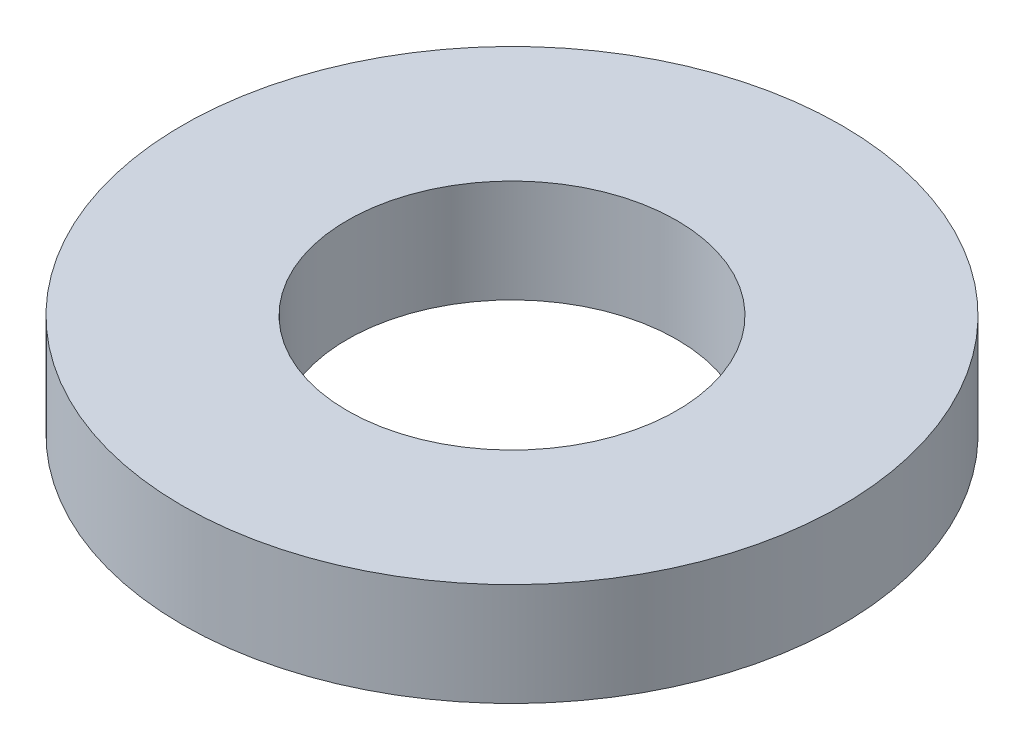
SolidWorks part; units mm, degrees
ref_plane "Front Plane" through (0, 0, 0) normal (0, 0, 1) x (1, 0, 0)
ref_plane "Top Plane" through (0, 0, 0) normal (0, 1, 0) x (1, 0, 0)
ref_plane "Right Plane" through (0, 0, 0) normal (1, 0, 0) x (0, 0, -1)
sketch "Sketch1" plane through (0, 0, 0) normal (0, 1, 0) x (1, 0, 0)
  circle A0 centre (0, 0) radius 80
  dimension "FLANGE_OD" = 160
extrude "Boss-Extrude1" add sketch "Sketch1" along normal blind 25
sketch "Sketch2" plane through (0, 0, 0) normal (0, 1, 0) x (1, 0, 0)
  circle A0 centre (0, 0) radius 40
  dimension "BORE_D" = 80
extrude "Cut-Extrude1" cut sketch "Sketch2" along normal through all
sketch "Sketch3" plane through (0, 25, 0) normal (0, 1, 0) x (1, 0, 0)
  circle A0 centre (0, 0) radius 30.0003 construction
  circle A1 centre (-30.0003, 0) radius 2.2405
  dimension "BOLT_D" = 4.4809
  dimension "BOLT_PCD" = 60.0005
extrude "Cut-Extrude2" cut sketch "Sketch3" against normal blind 20.7777 rebuild error yes
pattern_circular "CirPattern1" count 3 over 360 rebuild error yes
